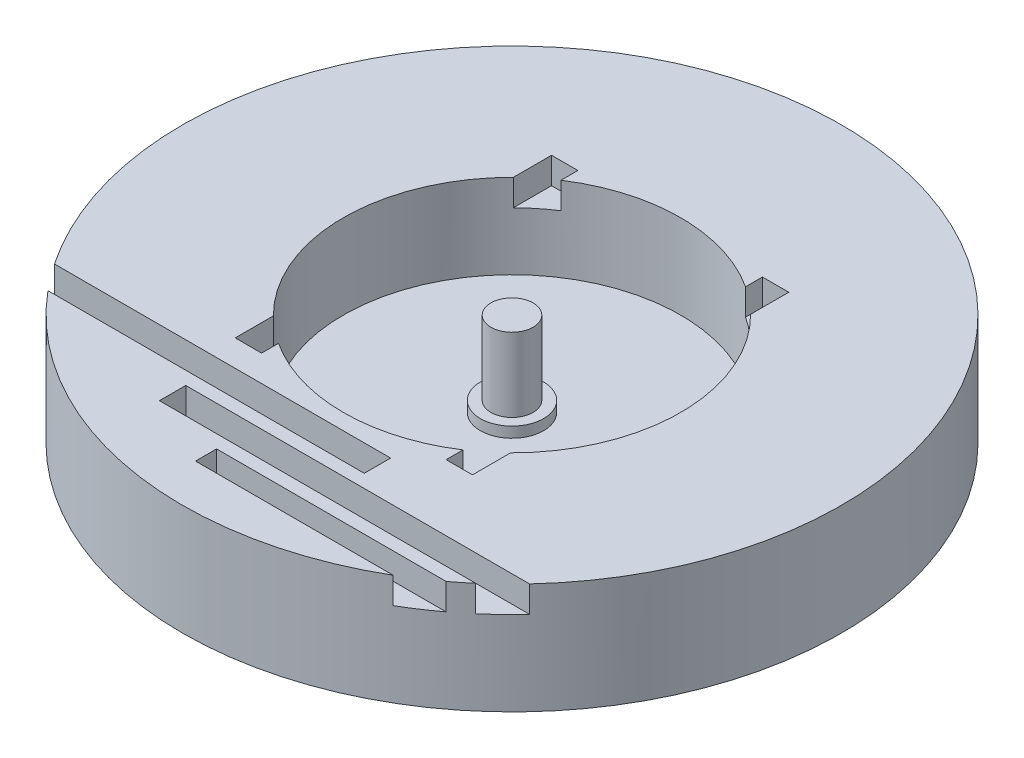
SolidWorks part; units mm, degrees
material "Cast Alloy Steel"
ref_plane "Front Plane" through (0, 0, 0) normal (0, 0, 1) x (1, 0, 0)
ref_plane "Top Plane" through (0, 0, 0) normal (0, 1, 0) x (1, 0, 0)
ref_plane "Right Plane" through (0, 0, 0) normal (1, 0, 0) x (0, 0, -1)
sketch "Sketch1" plane through (0, 0, 0) normal (0, 1, 0) x (1, 0, 0)
  circle A0 centre (0, 0) radius 62.5
  dimension "D1" = 125
extrude "Boss-Extrude1" add sketch "Sketch1" along normal blind 21
sketch "Sketch2" plane through (0, 21, 0) normal (0, 1, 0) x (1, 0, 0)
  circle A0 centre (0, 0) radius 32
  circle A1 centre (0, 0) radius 6
  dimension "D1" = 64
extrude "Cut-Extrude1" cut sketch "Sketch2" against normal blind 16
sketch "Sketch3" plane through (0, 21, 0) normal (0, 1, 0) x (1, 0, 0)
  circle A0 centre (0, 0) radius 6
  circle A1 centre (0, 0) radius 4
extrude "Cut-Extrude2" cut sketch "Sketch3" against normal blind 14
sketch "Sketch10" plane through (0, 21, 0) normal (0, 1, 0) x (1, 0, 0)
  line L0 (-20, 0) -> (20, 0) construction
  line L2 (-22.5, -30) -> (-17.5, -30)
  line L3 (-22.5, -30) -> (-22.5, 30)
  line L4 (-22.5, 30) -> (-17.5, 30)
  line L5 (-17.5, -30) -> (-17.5, 30)
  line L6 (-22.5, -30) -> (-17.5, 30) construction
  line L7 (-22.5, 30) -> (-17.5, -30) construction
  line L8 (22.5, -30) -> (17.5, -30)
  line L9 (22.5, -30) -> (22.5, 30)
  line L10 (22.5, 30) -> (17.5, 30)
  line L11 (17.5, -30) -> (17.5, 30)
  line L12 (22.5, -30) -> (17.5, 30) construction
  line L13 (22.5, 30) -> (17.5, -30) construction
  point P5 (0, 0)
  dimension "D1" = 40
  dimension "D2" = 60
  dimension "D3" = 60
  dimension "D4" = 5
  dimension "D5" = 5
extrude "Cut-Extrude7" cut sketch "Sketch10" against normal blind 5
sketch "Sketch4" plane through (0, 21, 0) normal (0, 1, 0) x (1, 0, 0)
  circle A0 centre (0, 0) radius 4
sketch "Sketch11" plane through (0, 21, 0) normal (0, 1, 0) x (1, 0, 0)
  line L0 (0, 0) -> (0, -35) construction
  line L1 (0, -40) -> (0, -42.5) construction
  line L2 (11.9766, -40) -> (-48.0234, -40)
  line L3 (11.9766, -40) -> (11.9766, -35)
  line L4 (11.9766, -35) -> (-51.7808, -35)
  line L5 (0, -47.5) -> (0, -50) construction
  line L6 (-19.3798, -47.5) -> (40.6202, -47.5)
  line L7 (-19.3798, -47.5) -> (-19.3798, -42.5)
  line L8 (-19.3798, -42.5) -> (45.8258, -42.5)
  line L10 (-6.0318, -54) -> (31.4682, -54)
  line L11 (-6.0318, -54) -> (-6.0318, -50)
  line L12 (-6.0318, -50) -> (37.5, -50)
  arc A0 (31.4682, -54) -> (37.5, -50) centre (0, 0) ccw
  arc A1 (-51.7808, -35) -> (-48.0234, -40) centre (0, 0) ccw
  arc A2 (40.6202, -47.5) -> (45.8258, -42.5) centre (0, 0) ccw
  dimension "D4" = 125
  dimension "D1" = 35
  dimension "D2" = 5
  dimension "D3" = 0
  dimension "D5" = 60
  dimension "D6" = 2.5
  dimension "D7" = 0
  dimension "D8" = 5
  dimension "D9" = 60
  dimension "D10" = 2.5
  dimension "D11" = 0
  dimension "D12" = 4
  dimension "D13" = 37.5
extrude "Cut-Extrude8" cut sketch "Sketch11" against normal blind 5
